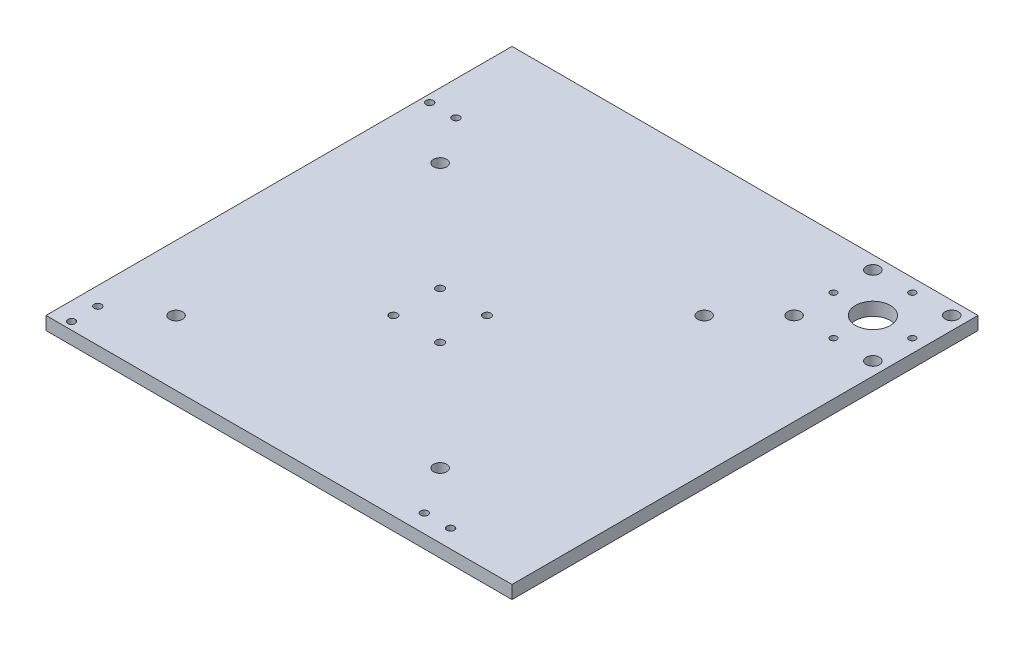
SolidWorks part; units mm, degrees
material "Perspex (TM) GS Acrylic Cast Sheet"
ref_plane "Front Plane" through (0, 0, 0) normal (0, 0, 1) x (1, 0, 0)
ref_plane "Top Plane" through (0, 0, 0) normal (0, 1, 0) x (1, 0, 0)
ref_plane "Right Plane" through (0, 0, 0) normal (1, 0, 0) x (0, 0, -1)
sketch "Sketch1" plane through (0, 0, 0) normal (0, 1, 0) x (1, 0, 0)
  line L1 (-95.25, -95.25) -> (95.25, -95.25)
  line L2 (-95.25, -95.25) -> (-95.25, 95.25)
  line L3 (-95.25, 95.25) -> (95.25, 95.25)
  line L4 (95.25, -95.25) -> (95.25, 95.25)
  line L5 (-15.875, -15.875) -> (15.875, -15.875)
  line L6 (-15.875, -15.875) -> (-15.875, 15.875)
  line L7 (-15.875, 15.875) -> (15.875, 15.875)
  line L8 (15.875, -15.875) -> (15.875, 15.875)
  circle A0 centre (-11.303, 11.303) radius 1.905
  circle A1 centre (-11.303, -11.303) radius 1.905
  circle A2 centre (11.303, 11.303) radius 1.905
  circle A3 centre (11.303, -11.303) radius 1.905
  circle A4 centre (-78.9, 86.55) radius 1.778
  circle A5 centre (-91.6, 86.55) radius 1.778
  circle A6 centre (91.6, -86.55) radius 1.778
  circle A7 centre (78.9, -86.55) radius 1.778
  circle A8 centre (-86.55, -78.9) radius 1.778
  circle A9 centre (-86.55, -91.6) radius 1.778
  circle A10 centre (0, 0) radius 6.35
  point P0 (0, 0)
  point P6 (0, 0)
  point P19 (-85.25, 92.9)
  point P24 (85.25, -92.9)
  point P29 (-92.9, -85.25)
  dimension "D5" = 4.572
  dimension "D10" = 12.7
  dimension "D18" = 12.7
  dimension "D1" = 190.5
  dimension "D2" = 190.5
  dimension "D3" = 31.75
  dimension "D4" = 31.75
  dimension "D6" = 4.572
  dimension "D7" = 4.572
  dimension "D8" = 92.9
  dimension "D9" = 85.25
  dimension "D11" = 4.572
  dimension "D12" = 6.35
  dimension "D13" = 6.35
  dimension "D14" = 92.9
  dimension "D15" = 85.25
  dimension "D16" = 6.35
  dimension "D17" = 6.35
  dimension "D19" = 85.25
  dimension "D20" = 92.9
  dimension "D21" = 6.35
  dimension "D22" = 6.35
  dimension "D23" = 12.7
extrude "Boss-Extrude1" add sketch "Sketch1" along normal blind 6.35 contours L4 L3 L2 L1 | A7 | A6 | A8 | A9 | A4 | A5 | A1 | A3 | A0 | A2
sketch "Sketch7" plane through (0, 0, 0) normal (0, -1, 0) x (1, 0, 0)
  line L0 (-130, -130) -> (78.2, -130) construction
  line L1 (130, -78.2) -> (130, 130) construction
  line L2 (-95.25, -130) -> (78.2, -130)
  line L3 (130, -78.2) -> (130, 95.25)
  line L4 (130, -78.2) -> (130, -130)
  line L5 (130, -130) -> (78.2, -130)
  line L6 (-95.25, -95.25) -> (-95.25, -130)
  line L7 (-95.25, -95.25) -> (95.25, -95.25)
  line L8 (95.25, -95.25) -> (95.25, 95.25)
  line L9 (95.25, 95.25) -> (130, 95.25)
extrude "Boss-Extrude3" add sketch "Sketch7" against normal up to surface (6.35 mm away) contours L2 L5 L4 L3 L9 L8 L7 L6 up to face at (-11.303, 6.35, -9.398)
sketch "Sketch8" plane through (0, 0, 0) normal (0, -1, 0) x (1, 0, 0)
  circle A0 centre (-63.7786, -63.7786) radius 3.175 construction
  circle A1 centre (-63.7786, 63.8746) radius 3.175 construction
  circle A2 centre (63.8746, 63.8746) radius 3.175 construction
  circle A3 centre (63.8746, -63.7786) radius 3.175 construction
  circle A4 centre (-63.7786, -63.7786) radius 3.175
  circle A5 centre (-63.7786, 63.8746) radius 3.175
  circle A6 centre (63.8746, 63.8746) radius 3.175
  circle A7 centre (63.8746, -63.7786) radius 3.175
extrude "Cut-Extrude1" cut sketch "Sketch8" against normal through all
sketch "Sketch9" plane through (0, 0, 0) normal (0, -1, 0) x (1, 0, 0)
  circle A0 centre (123.65, -123.65) radius 3.175 construction
  circle A1 centre (85.55, -85.55) radius 3.175 construction
  circle A2 centre (123.65, -85.55) radius 3.175 construction
  circle A3 centre (123.65, -123.65) radius 3.175
  circle A4 centre (85.55, -85.55) radius 3.175
  circle A5 centre (123.65, -85.55) radius 3.175
  circle A7 centre (85.55, -123.65) radius 3.175
  circle A8 centre (85.55, -123.65) radius 3.175
  dimension "D1" = 0
extrude "Cut-Extrude2" cut sketch "Sketch9" against normal through all
sketch "Sketch10" plane through (0, 0, 0) normal (0, -1, 0) x (1, 0, 0)
  circle A0 centre (104.6, -123.65) radius 1.5875 construction
  circle A1 centre (85.55, -104.6) radius 1.5875 construction
  circle A2 centre (104.6, -85.55) radius 1.5875 construction
  circle A3 centre (123.65, -104.6) radius 1.5875 construction
  circle A4 centre (104.6, -123.65) radius 1.5875
  circle A5 centre (85.55, -104.6) radius 1.5875
  circle A6 centre (104.6, -85.55) radius 1.5875
  circle A7 centre (123.65, -104.6) radius 1.5875
extrude "Cut-Extrude3" cut sketch "Sketch10" against normal through all
sketch "Sketch11" plane through (0, 0, 0) normal (0, -1, 0) x (1, 0, 0)
  circle A0 centre (104.6, -104.6) radius 8.4138 construction
  circle A1 centre (104.6, -104.6) radius 8.4138
extrude "Cut-Extrude4" cut sketch "Sketch11" against normal through all
